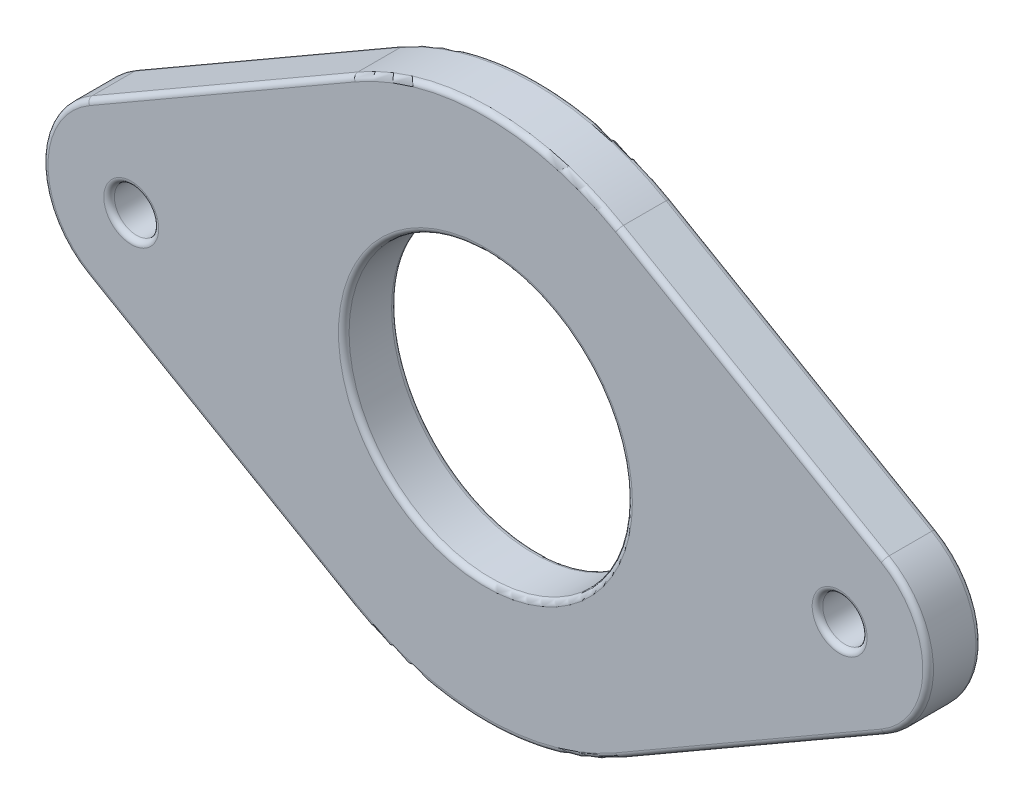
SolidWorks part; units mm, degrees
ref_plane "Front Plane" through (0, 0, 0) normal (0, 0, 1) x (1, 0, 0)
ref_plane "Top Plane" through (0, 0, 0) normal (0, 1, 0) x (1, 0, 0)
ref_plane "Right Plane" through (0, 0, 0) normal (1, 0, 0) x (0, 0, -1)
sketch "Sketch1" plane through (0, 0, 0) normal (0, 0, 1) x (1, 0, 0)
  line L0 (-20, 0) -> (20, 0) construction
  line L1 (-22.5, 4.3301) -> (-7.5, 12.9904)
  line L2 (7.5, 12.9904) -> (22.5, 4.3301)
  line L3 (-22.5, -4.3301) -> (-7.5, -12.9904)
  line L4 (7.5, -12.9904) -> (22.5, -4.3301)
  arc A0 (-7.5, -12.9904) -> (7.5, -12.9904) centre (0, 0) ccw
  circle A1 centre (-20, 0) radius 1.25
  circle A2 centre (20, 0) radius 1.25
  arc A3 (22.5, -4.3301) -> (22.5, 4.3301) centre (20, 0) ccw
  arc A4 (-22.5, 4.3301) -> (-22.5, -4.3301) centre (-20, 0) ccw
  arc A5 (7.5, 12.9904) -> (-7.5, 12.9904) centre (0, 0) ccw
  circle A6 centre (0, 0) radius 8
  dimension "D1" = 30
  dimension "D3" = 2.5
  dimension "D4" = 10
  dimension "D5" = 16
  dimension "D2" = 20
extrude "Boss-Extrude1" add sketch "Sketch1" along normal blind 3
fillet "Fillet1" radius 0.3 22 edges at (21.25, 0, 0) (-18.75, 0, 0) (8, 0, 0) (-15, -8.6603, 0) (0, -15, 0) (15, -8.6603, 0) (25, 0, 0) (15, 8.6603, 0) (0, 15, 0) (-15, 8.6603, 0) (-25, 0, 0) (21.25, 0, 3) (8, 0, 3) (-15, 8.6603, 3) (0, 15, 3) (15, 8.6603, 3) (25, 0, 3) (15, -8.6603, 3) (0, -15, 3) (-15, -8.6603, 3) (-25, 0, 3) (-18.75, 0, 3)
